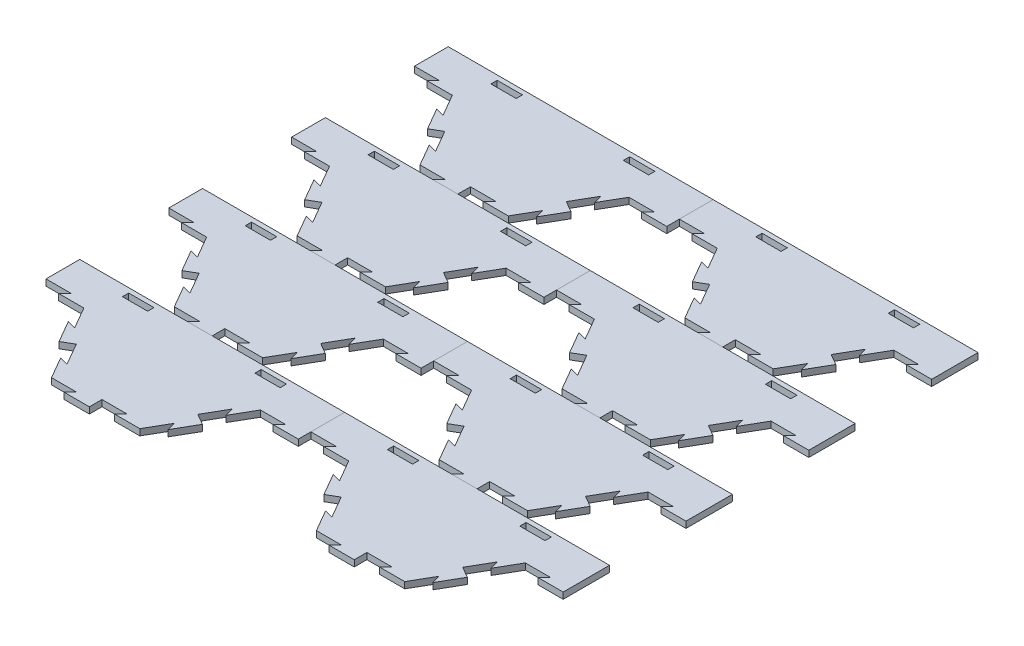
SolidWorks part; units mm, degrees
material "Cedar"
ref_plane "Front Plane" through (0, 0, 0) normal (0, 0, 1) x (1, 0, 0)
ref_plane "Top Plane" through (0, 0, 0) normal (0, 1, 0) x (1, 0, 0)
ref_plane "Right Plane" through (0, 0, 0) normal (1, 0, 0) x (0, 0, -1)
sketch "Sketch1" plane through (0, 0, 0) normal (0, 1, 0) x (1, 0, 0)
  line L0 (0, 0) -> (88.9, 0) construction
  line L1 (88.9, 0) -> (44.45, 76.9897)
  line L2 (44.45, 76.9897) -> (-44.45, 76.9897)
  line L3 (-44.45, 76.9897) -> (-88.9, 0)
  line L4 (-88.9, 0) -> (-44.45, -76.9897)
  line L5 (-44.45, -76.9897) -> (44.45, -76.9897)
  line L6 (44.45, -76.9897) -> (88.9, 0)
  circle A0 centre (0, 0) radius 76.9897 construction
  dimension "D1" = 88.9
extrude "Boss-Extrude1" add sketch "Sketch1" against normal blind 6.35
sketch "Sketch2" plane through (0, 0, 0) normal (0, 1, 0) x (1, 0, 0)
  point P1 (0, 0)
ref_axis "Axis1" through (0, 0, 0) along (0, 1, 0)
sketch "Sketch10" plane through (0, 0, 0) normal (0, 1, 0) x (1, 0, 0)
  line L0 (44.45, 76.9897) -> (57.15, 54.9926) construction
  line L1 (57.15, 54.9926) -> (48.4757, 57.3169)
  line L2 (48.4757, 57.3169) -> (61.1757, 35.3198)
  line L3 (61.1757, 35.3198) -> (66.675, 38.4948)
  line L4 (57.15, 54.9926) -> (66.675, 38.4948)
  line L5 (88.9, 0) -> (44.45, 76.9897) construction
  dimension "D1" = 45
  dimension "D2" = 6.35
extrude "Cut-Extrude4" cut sketch "Sketch10" against normal through all
sketch "Sketch11" plane through (0, 0, 0) normal (0, 1, 0) x (1, 0, 0)
  line L0 (66.675, 38.4948) -> (88.9, 0) construction
  line L1 (66.675, 38.4948) -> (72.1743, 41.6698)
  line L2 (72.1743, 41.6698) -> (84.8743, 19.6728)
  line L3 (84.8743, 19.6728) -> (76.2, 21.997)
  line L4 (76.2, 21.997) -> (66.675, 38.4948)
  line L5 (76.2, 21.997) -> (88.9, 0) construction
  line L6 (76.2, 21.997) -> (88.9, 0) construction
  line L7 (88.9, 0) -> (66.675, 38.4948) construction
  line L8 (44.45, -76.9897) -> (88.9, 0) construction
  dimension "D1" = 45
  dimension "D2" = 6.35
extrude "Boss-Extrude4" add sketch "Sketch11" against normal blind 6.35
pattern_circular "CirPattern7" count 6 over 360 about axis through (0, 0, 0) along (0, 1, 0) of "Cut-Extrude4", "Boss-Extrude4"
sketch "Sketch12" plane through (0, 0, 0) normal (0, 1, 0) x (1, 0, 0)
  line L0 (-88.9, 0) -> (88.9, 0)
  line L1 (88.9, 0) -> (88.9, 83.3397)
  line L2 (88.9, 83.3397) -> (-88.9, 83.3397)
  line L3 (-88.9, 83.3397) -> (-88.9, 0)
extrude "Cut-Extrude5" cut sketch "Sketch12" against normal through all
sketch "Sketch13" plane through (0, 0, 0) normal (0, 0, -1) x (-1, 0, 0)
  line L0 (0, -6.35) -> (0, 0) construction
  line L1 (133.35, -6.35) -> (-133.35, -6.35)
  line L2 (133.35, -6.35) -> (133.35, 0)
  line L3 (133.35, 0) -> (-133.35, 0)
  line L4 (-133.35, -6.35) -> (-133.35, 0)
  line L5 (88.9, -6.35) -> (-88.9, -6.35) construction
  dimension "D1" = 266.7
extrude "Boss-Extrude5" add sketch "Sketch13" along normal blind 40.3279
sketch "Sketch15" plane through (0, 0, 0) normal (0, 1, 0) x (1, 0, 0)
  line L0 (-88.9, 0) -> (-114.3, 0) construction
  line L1 (-114.3, 0) -> (-107.95, 6.35)
  line L2 (-107.95, 6.35) -> (-133.35, 6.35)
  line L3 (-133.35, 6.35) -> (-133.35, 0)
  line L4 (-114.3, 0) -> (-133.35, 0)
  line L6 (-133.35, 0) -> (-88.9, 0) construction
  line L7 (-133.35, 40.3279) -> (-133.35, 0) construction
  dimension "D1" = 45
  dimension "D2" = 6.35
extrude "Cut-Extrude6" cut sketch "Sketch15" against normal through all
sketch "Sketch16" plane through (0, 0, 0) normal (0, 1, 0) x (1, 0, 0)
  line L0 (88.9, 0) -> (114.3, 0) construction
  line L1 (114.3, 0) -> (107.95, -6.35)
  line L2 (107.95, -6.35) -> (133.35, -6.35)
  line L3 (133.35, -6.35) -> (133.35, 0)
  line L4 (114.3, 0) -> (133.35, 0)
  dimension "D1" = 45
  dimension "D2" = 6.35
extrude "Boss-Extrude6" add sketch "Sketch16" against normal up to surface (6.35 mm away) up to face at (-7.9375, -6.35, 35.1607)
sketch "Sketch17" plane through (0, 0, 0) normal (0, 1, 0) x (1, 0, 0)
  line L0 (0, 40.3279) -> (0, 24.6809) construction
  line L1 (-66.675, 32.5044) -> (66.675, 32.5044) construction
  line L2 (-79.375, 35.6794) -> (-53.975, 35.6794)
  line L3 (-79.375, 35.6794) -> (-79.375, 29.3294)
  line L4 (-79.375, 29.3294) -> (-53.975, 29.3294)
  line L5 (-53.975, 35.6794) -> (-53.975, 29.3294)
  line L6 (-79.375, 35.6794) -> (-53.975, 29.3294) construction
  line L7 (-79.375, 29.3294) -> (-53.975, 35.6794) construction
  line L8 (53.975, 35.6794) -> (79.375, 35.6794)
  line L9 (53.975, 35.6794) -> (53.975, 29.3294)
  line L10 (53.975, 29.3294) -> (79.375, 29.3294)
  line L11 (79.375, 35.6794) -> (79.375, 29.3294)
  line L12 (53.975, 35.6794) -> (79.375, 29.3294) construction
  line L13 (53.975, 29.3294) -> (79.375, 35.6794) construction
  line L14 (-133.35, 40.3279) -> (133.35, 40.3279) construction
  line L15 (-133.35, 24.6809) -> (133.35, 24.6809) construction
  line L16 (-133.35, 40.3279) -> (-133.35, 6.35) construction
  line L17 (133.35, 40.3279) -> (133.35, -6.35) construction
  point P4 (0, 32.5044)
  point P5 (0, 32.5044)
  dimension "D1" = 6.35
  dimension "D2" = 25.4
  dimension "D3" = 6.35
  dimension "D4" = 25.4
  dimension "D5" = 133.35
  dimension "D6" = 15.6471
extrude "Cut-Extrude8" cut sketch "Sketch17" against normal through all
pattern_linear "LPattern1" count 2 spacing 266.7 along (1, 0, 0) of bodies 135
pattern_linear "LPattern2" count 4 spacing 123.6676 along (0, 0, 1) of bodies 135 136
